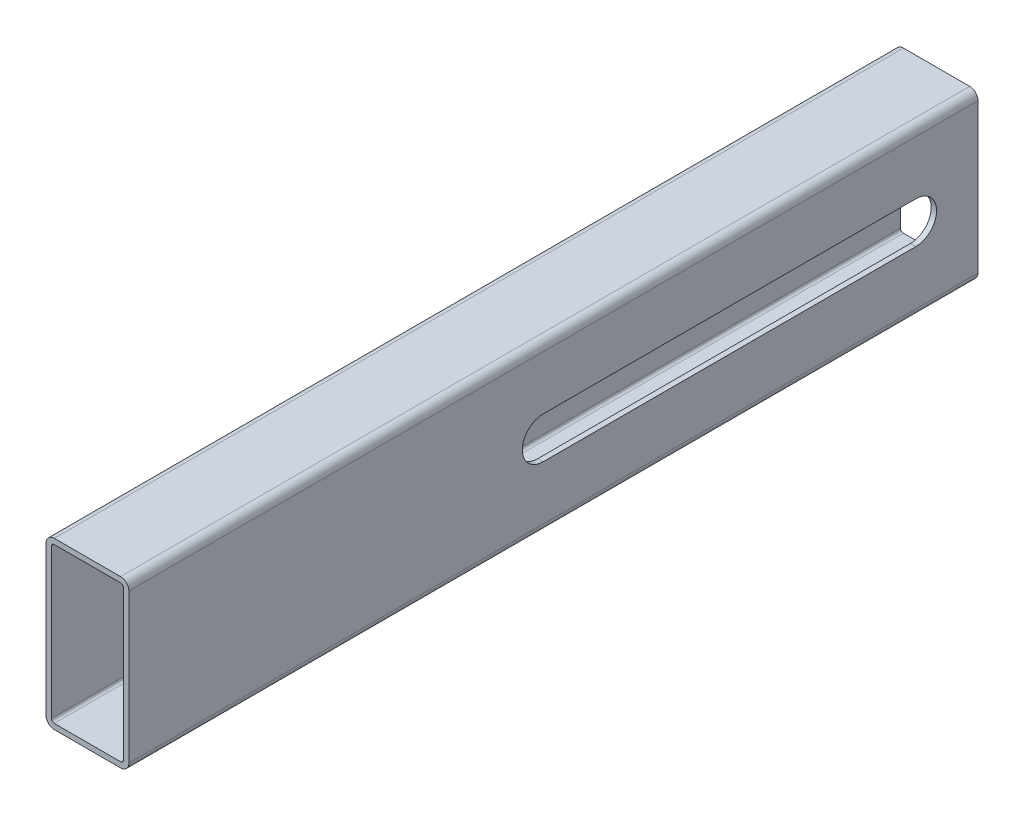
SolidWorks part; units mm, degrees
material "6061-T6 (SS)"
ref_plane "Front Plane" through (0, 0, 0) normal (0, 0, 1) x (1, 0, 0)
ref_plane "Top Plane" through (0, 0, 0) normal (0, 1, 0) x (1, 0, 0)
ref_plane "Right Plane" through (0, 0, 0) normal (1, 0, 0) x (0, 0, -1)
sketch "Sketch1" plane through (0, 0, 0) normal (0, 0, 1) x (1, 0, 0)
  line L1 (10.16, -25.4) -> (-10.16, -25.4)
  line L2 (12.7, -22.86) -> (12.7, 22.86)
  line L3 (10.16, 25.4) -> (-10.16, 25.4)
  line L4 (-12.7, -22.86) -> (-12.7, 22.86)
  line L5 (12.7, -25.4) -> (-12.7, 25.4) construction
  line L6 (12.7, 25.4) -> (-12.7, -25.4) construction
  arc A0 (-10.16, -25.4) -> (-12.7, -22.86) centre (-10.16, -22.86) cw
  arc A1 (10.16, -25.4) -> (12.7, -22.86) centre (10.16, -22.86) ccw
  arc A2 (12.7, 22.86) -> (10.16, 25.4) centre (10.16, 22.86) ccw
  arc A3 (-10.16, 25.4) -> (-12.7, 22.86) centre (-10.16, 22.86) ccw
  point P0 (0, 0)
  dimension "D3" = 2.54
  dimension "D1" = 25.4
  dimension "D2" = 50.8
extrude "Extrude-Thin1" add sketch "Sketch1" along normal blind 260.35 thin thin type one direction reverse wall 1.651
sketch "Sketch2" plane through (-12.7, 0, 0) normal (-1, 0, 0) x (0, 0, 1)
  line L0 (19.05, 0) -> (133.35, 0) construction
  line L1 (19.05, 6.35) -> (133.35, 6.35)
  line L2 (19.05, -6.35) -> (133.35, -6.35)
  line L3 (0, 22.86) -> (0, -22.86) construction
  arc A0 (19.05, 6.35) -> (19.05, -6.35) centre (19.05, 0) ccw
  arc A1 (133.35, -6.35) -> (133.35, 6.35) centre (133.35, 0) ccw
  point P3 (76.2, 0)
  dimension "D1" = 12.7
  dimension "D2" = 114.3
  dimension "D3" = 19.05
extrude "Cut-Extrude1" cut sketch "Sketch2" against normal through all
sketch "Sketch3" [suppressed] plane through (-12.7, 0, 0) normal (-1, 0, 0) x (0, 0, 1)
  line L0 (571.5, 0) -> (444.5, 0) construction
  line L1 (571.5, -6.35) -> (444.5, -6.35)
  line L2 (571.5, 6.35) -> (444.5, 6.35)
  line L3 (736.6, 22.86) -> (736.6, -22.86) construction
  arc A0 (571.5, -6.35) -> (571.5, 6.35) centre (571.5, 0) ccw
  arc A1 (444.5, 6.35) -> (444.5, -6.35) centre (444.5, 0) ccw
  point P3 (508, 0)
  dimension "D1" = 12.7
  dimension "D2" = 165.1
  dimension "D3" = 127
extrude "Cut-Extrude2" [suppressed] cut sketch "Sketch3" against normal through all
